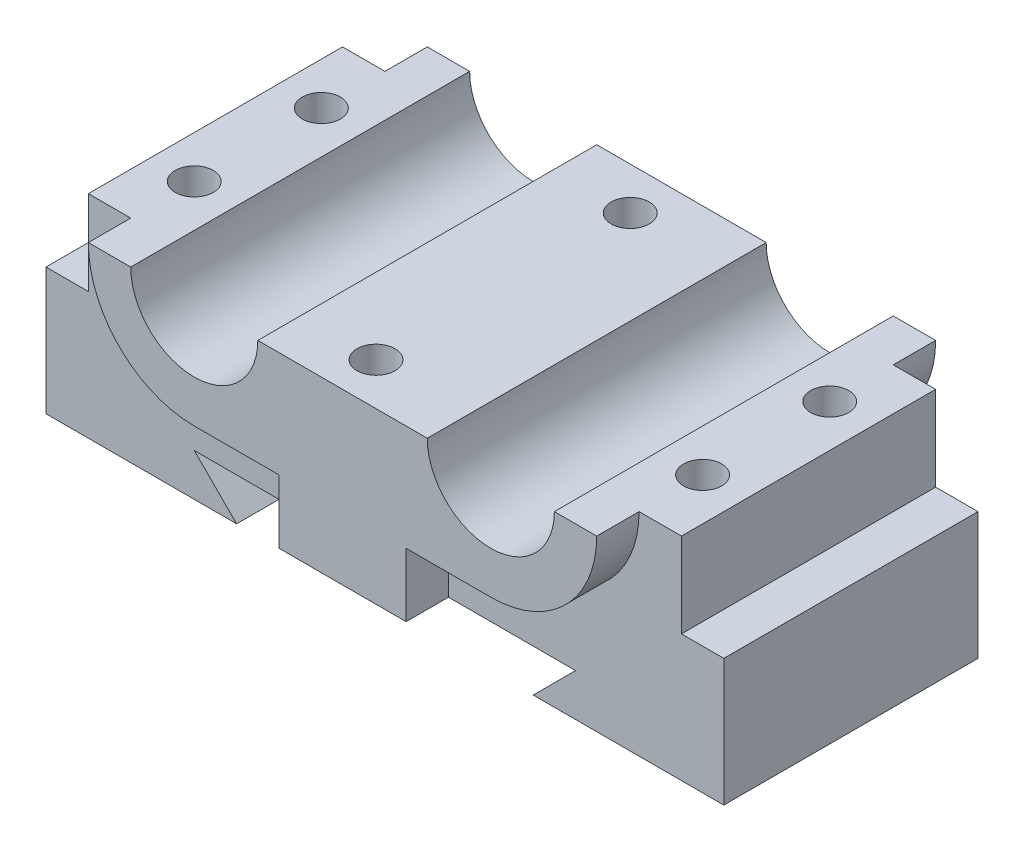
SolidWorks part; units mm, degrees
ref_plane "Front Plane" through (0, 0, 0) normal (0, 0, 1) x (1, 0, 0)
ref_plane "Top Plane" through (0, 0, 0) normal (0, 1, 0) x (1, 0, 0)
ref_plane "Right Plane" through (0, 0, 0) normal (1, 0, 0) x (0, 0, -1)
sketch "Sketch1" plane through (0, 0, 0) normal (0, 0, 1) x (1, 0, 0)
  line L0 (-56.0986, 0) -> (86.0964, 0) construction
  line L1 (-16.0986, 42.4984) -> (-16.0986, -72.3968) construction
  line L2 (-56.0986, 0) -> (-33.5986, 0)
  line L3 (-33.5986, 0) -> (-38.5986, 5)
  line L4 (-38.5986, 5) -> (6.4014, 5)
  line L5 (-56.0986, 0) -> (-56.0986, 15)
  line L6 (-56.0986, 15) -> (-51.0986, 15)
  line L7 (-51.0986, 15) -> (-51.0986, 25)
  line L8 (-51.0986, 25) -> (-41.0986, 25)
  line L9 (-26.0986, 25) -> (-6.0986, 25)
  line L10 (23.9014, 15) -> (18.9014, 15)
  line L11 (1.4014, 0) -> (6.4014, 5)
  line L12 (23.9014, 0) -> (1.4014, 0)
  line L13 (23.9014, 0) -> (23.9014, 15)
  line L14 (18.9014, 15) -> (18.9014, 25)
  line L15 (18.9014, 25) -> (8.9014, 25)
  line L16 (-23.5986, 5) -> (-23.5986, 12.5)
  line L17 (-23.5986, 12.5) -> (-33.5986, 12.5)
  line L18 (-8.5986, 5) -> (-8.5986, 12.5)
  line L19 (-8.5986, 12.5) -> (1.4014, 12.5)
  arc A0 (-41.0986, 25) -> (-26.0986, 25) centre (-33.5986, 25) ccw
  arc A1 (8.9014, 25) -> (-6.0986, 25) centre (1.4014, 25) cw
  arc A2 (-33.5986, 12.5) -> (-46.0986, 25) centre (-33.5986, 25) cw
  arc A3 (1.4014, 12.5) -> (13.9014, 25) centre (1.4014, 25) ccw
  dimension "D7" = 7.5
  dimension "D11" = 12.5
  dimension "D1" = 45
  dimension "D2" = 5
  dimension "D3" = 22.5
  dimension "D4" = 15
  dimension "D5" = 5
  dimension "D6" = 10
  dimension "D8" = 17.5
  dimension "D9" = 35
  dimension "D10" = 22.5
  dimension "D12" = 15
extrude "Boss-Extrude1" add sketch "Sketch1" along normal mid plane 40 contours L19 A3 L15 A1 L9 A0 L8 A2 L17 L16 L4 L18 region at (-16.0986, 16.4306, 0)
extrude "Boss-Extrude2" add sketch "Sketch1<3>" along normal mid plane 30 contours A3 L19 L18 L4 L11 L12 L13 L10 L14 L15 | L17 A2 L8 L7 L6 L5 L2 L3 L4 L16 region at (-43.0645, 9.3502, 0) region at (10.8673, 9.3502, 0)
sketch "Sketch1<3>" plane through (0, 0, 0) normal (0, 0, 1) x (1, 0, 0) same geometry as "Sketch1"
hole_wizard "Ø1.0mm Dowel Hole1" positions "Sketch3" profile "Sketch4" hole size "Ø1.0" standard "ANSI Metric"
sketch "Sketch3" plane through (0, 25, 0) normal (0, 1, 0) x (1, 0, 0)
  line L0 (-41.0986, -20) -> (-26.0986, -20) construction
  line L1 (-6.0986, -20) -> (8.9014, -20) construction
  line L5 (0, 0) -> (25.0648, 0) construction
  point P0 (-17.1466, 15)
  point P2 (13.9014, 7.5)
  point P4 (-46.0986, 7.5)
  point P9 (-33.5986, -20)
  point P12 (1.4014, -20)
  point P25 (0, 0)
  point P26 (0, 0)
  point P29 (0, 0)
  point P30 (0, 0)
  point P31 (-17.1466, 15)
  point P32 (0, 0)
  dimension "D1" = 12.5
  dimension "D2" = 12.5
  dimension "D4" = 15
  dimension "D5" = 30
sketch "Sketch4" plane through (-17.1466, 25, -15) normal (1, 0, 0) x (0, 0, 1)
  line L0 (0, 0) -> (0, 16.299)
  line L1 (0, 16.299) -> (2.25, 15)
  line L2 (2.25, 15) -> (2.25, 0)
  line L5 (2.25, 0) -> (0, 0)
  line L10 (0, 16.299) -> (-2.25, 15) construction
  line L11 (0, -6.35) -> (0, 107.95) construction
  dimension "Hole Dia." = 4.5
  dimension "Hole Depth" = 15
  dimension "Drill Angle" = 120
ref_plane "Plane1" through (0, 0, 0) normal (0, 0, 1) x (1, 0, 0)
mirror "Mirror1" about plane through (0, 0, 0) normal (0, 0, 1) of "Ø1.0mm Dowel Hole1"
